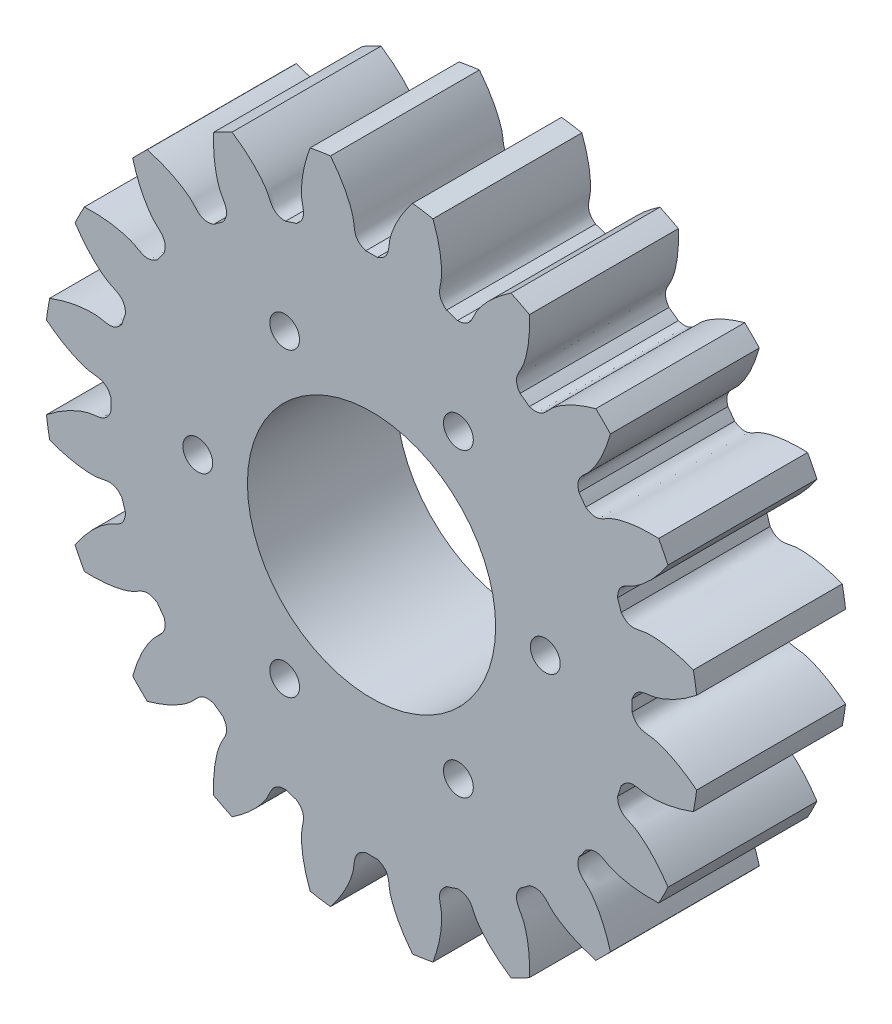
SolidWorks part; units mm, degrees
ref_plane "前视基准面" through (0, 0, 0) normal (0, 0, 1) x (1, 0, 0)
ref_plane "上视基准面" through (0, 0, 0) normal (0, 1, 0) x (1, 0, 0)
ref_plane "右视基准面" through (0, 0, 0) normal (1, 0, 0) x (0, 0, -1)
sketch "草图1" plane through (0, 0, 0) normal (0, 0, 1) x (1, 0, 0)
  circle A0 centre (0, 0) radius 66
extrude "凸台-拉伸1" add sketch "草图1" along normal blind 30
ref_axis "基准轴1" through (0, 0, -1.5) along (0, 0, 1)
sketch "草图2" plane through (0, 0, 0) normal (0, 0, 1) x (1, 0, 0)
  line L0 (0, 0) -> (0, 66) construction
  circle A0 centre (0, 0) radius 66 construction
  arc A1 (1.1599, 52.4872) -> (-1.1599, 52.4872) centre (0, 0) ccw
  arc A2 (19.0869, 74.9895) -> (-19.0869, 74.9895) centre (0, 0) ccw
  spline S0 degree 3 poles (1.1599, 52.4872) (3.6671, 53.3609) (3.3425, 55.1227) (3.6774, 56.8201) (3.7134, 56.9853) (3.7579, 57.1718) (3.8118, 57.3792) (3.8759, 57.6071) (3.9511, 57.8554) (4.0382, 58.1235) (4.138, 58.4111) (4.2514, 58.7179) (4.3791, 59.0433) (4.522, 59.3869) (4.6808, 59.7483) (4.8562, 60.1268) (5.0491, 60.5221) (5.2601, 60.9335) (5.49, 61.3604) (5.7395, 61.8023) (6.0092, 62.2586) (6.2999, 62.7285) (6.6121, 63.2115) (6.9466, 63.7068) (7.3039, 64.2138) (7.6846, 64.7317) (8.0893, 65.2598) (8.5185, 65.7973) (8.9729, 66.3435) (9.4528, 66.8975) (9.9589, 67.4586) (10.4914, 68.0259) (11.051, 68.5985) (11.638, 69.1757) (12.2528, 69.7564) (12.8958, 70.34) (13.5674, 70.9254) (14.2678, 71.5117) (14.9974, 72.098) (15.7564, 72.6834) (16.5451, 73.2669) (17.6488, 74.0498) (18.5036, 74.618) (19.0869, 74.9895) knots 0 0 0 0 0.165916 0.170906 0.176664 0.183189 0.190482 0.198542 0.207371 0.216967 0.22733 0.238462 0.250361 0.263027 0.276462 0.290664 0.305634 0.321371 0.337876 0.355149 0.37319 0.391998 0.411574 0.431917 0.453028 0.474907 0.497554 0.520968 0.54515 0.570099 0.595817 0.622302 0.649554 0.677575 0.706363 0.735918 0.766242 0.797333 0.829191 0.861818 0.895212 0.929373 1 1 1 1
  spline S1 degree 3 poles (-1.1599, 52.4872) (-3.6671, 53.3609) (-3.3425, 55.1227) (-3.6774, 56.8201) (-3.7134, 56.9853) (-3.7579, 57.1718) (-3.8118, 57.3792) (-3.8759, 57.6071) (-3.9511, 57.8554) (-4.0382, 58.1235) (-4.138, 58.4111) (-4.2514, 58.7179) (-4.3791, 59.0433) (-4.522, 59.3869) (-4.6808, 59.7483) (-4.8562, 60.1268) (-5.0491, 60.5221) (-5.2601, 60.9335) (-5.49, 61.3604) (-5.7395, 61.8023) (-6.0092, 62.2586) (-6.2999, 62.7285) (-6.6121, 63.2115) (-6.9466, 63.7068) (-7.3039, 64.2138) (-7.6846, 64.7317) (-8.0893, 65.2598) (-8.5185, 65.7973) (-8.9729, 66.3435) (-9.4528, 66.8975) (-9.9589, 67.4586) (-10.4914, 68.0259) (-11.051, 68.5985) (-11.638, 69.1757) (-12.2528, 69.7564) (-12.8958, 70.34) (-13.5674, 70.9254) (-14.2678, 71.5117) (-14.9974, 72.098) (-15.7564, 72.6834) (-16.5451, 73.2669) (-17.6488, 74.0498) (-18.5036, 74.618) (-19.0869, 74.9895) knots 0 0 0 0 0.165916 0.170906 0.176664 0.183189 0.190482 0.198542 0.207371 0.216967 0.22733 0.238462 0.250361 0.263027 0.276462 0.290664 0.305634 0.321371 0.337876 0.355149 0.37319 0.391998 0.411574 0.431917 0.453028 0.474907 0.497554 0.520968 0.54515 0.570099 0.595817 0.622302 0.649554 0.677575 0.706363 0.735918 0.766242 0.797333 0.829191 0.861818 0.895212 0.929373 1 1 1 1
extrude "切除-拉伸1" cut sketch "草图2" along normal through all
pattern_circular "阵列(圆周)1" count 20 every 18 about axis through (0, 0, -1.5) along (0, 0, 1) of "切除-拉伸1"
sketch "草图3" plane through (0, 0, 0) normal (0, 0, 1) x (1, 0, 0)
  circle A0 centre (0, 0) radius 60 construction
  dimension "Dn" = 120
sketch "草图4" plane through (0, 0, 30) normal (0, 0, 1) x (1, 0, 0)
  circle A0 centre (0, 0) radius 35
  circle A1 centre (-35, 0) radius 3
  circle A2 centre (-17.5, 30.3109) radius 3
  circle A3 centre (17.5, 30.3109) radius 3
  circle A4 centre (35, 0) radius 3
  circle A5 centre (17.5, -30.3109) radius 3
  circle A6 centre (-17.5, -30.3109) radius 3
  point P18 (0, 0)
  dimension "D1" = 70
  dimension "D2" = 6
extrude "切除-拉伸3" cut sketch "草图4" against normal blind 100 contours A1 | A2 | A3 | A4 | A5 | A6
sketch "草图5" plane through (0, 0, 30) normal (0, 0, 1) x (1, 0, 0)
  circle A0 centre (0, 0) radius 25
extrude "切除-拉伸4" cut sketch "草图5" against normal blind 50
